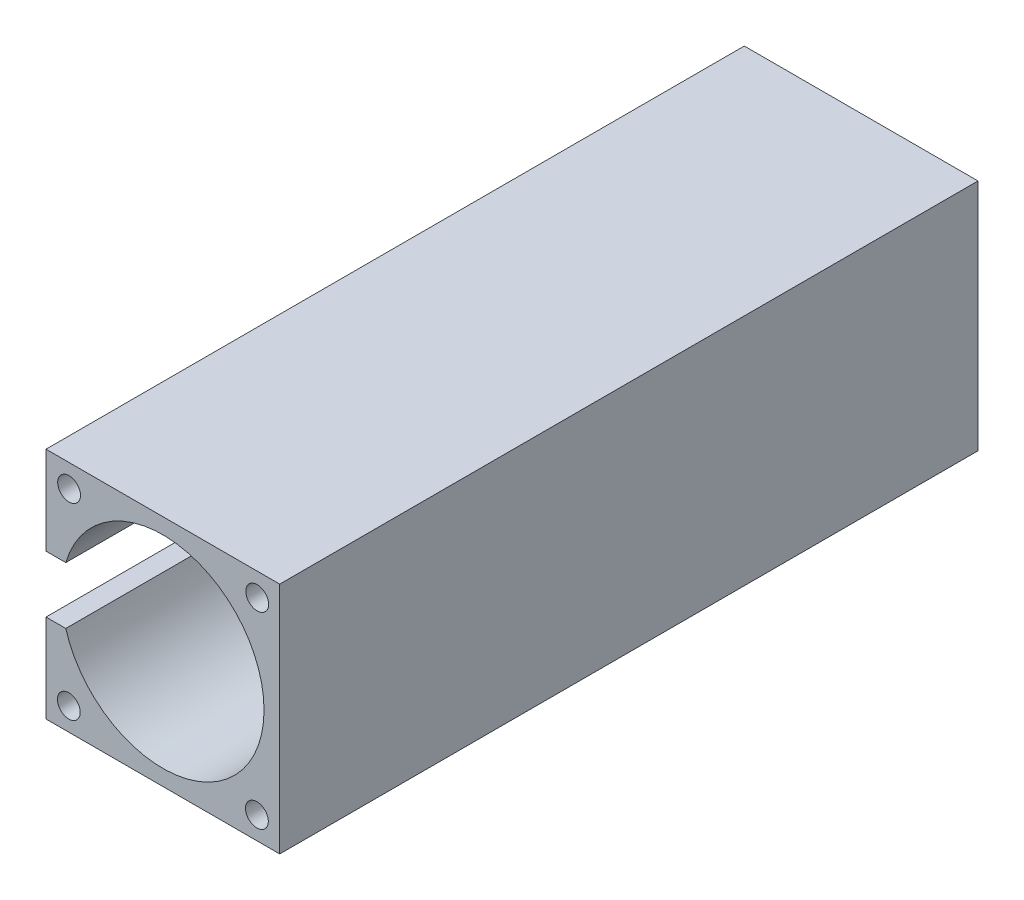
SolidWorks part; units mm, degrees
ref_plane "前基準面" through (0, 0, 0) normal (0, 0, 1) x (1, 0, 0)
ref_plane "上基準面" through (0, 0, 0) normal (0, 1, 0) x (1, 0, 0)
ref_plane "右基準面" through (0, 0, 0) normal (1, 0, 0) x (0, 0, -1)
ref_axis "基準軸1" through (0, -55, 0) along (0, 1, 0)
ref_axis "基準軸2" through (-88.99, 0, 0) along (1, 0, 0)
ref_axis "基準軸3" through (0, 0, 55) along (0, 0, -1)
sketch "草圖1" plane through (0, 0, 0) normal (0, 0, 1) x (1, 0, 0)
  line L0 (0, -55) -> (0, 55) construction
  line L1 (-41, -41) -> (41, -41)
  line L2 (-41, -41) -> (-41, 41)
  line L3 (-41, 41) -> (41, 41)
  line L4 (41, -41) -> (41, 41)
  line L5 (55, 0) -> (-55, 0) construction
  circle A0 centre (0, 0) radius 35.5
  point P7 (0, -41)
  point P10 (41, 0)
  dimension "D1" = 71
  dimension "D2" = 82
  dimension "D3" = 82
extrude "填料-伸長1" add sketch "草圖1" along normal blind 245
sketch "草圖2" plane through (0, 0, 0) normal (0, 0, -1) x (-1, 0, 0)
  line L1 (-41, 41) -> (41, 41)
  line L2 (-41, 41) -> (-41, -41)
  line L3 (-41, -41) -> (41, -41)
  line L4 (41, 41) -> (41, -41)
extrude "填料-伸長2" add sketch "草圖2" along normal blind 27
ref_plane "平面1" through (0, 0, -13.5) normal (0, 0, -1) x (-1, 0, 0)
sketch "草圖3" plane through (0, 0, 245) normal (0, 0, 1) x (1, 0, 0)
  line L0 (-41, 41) -> (-41, -41) construction
  line L1 (-41, 10) -> (-33, 10)
  line L2 (-41, 10) -> (-41, -10)
  line L3 (-41, -10) -> (-33, -10)
  line L4 (-33, 10) -> (-33, -10)
  line L6 (55, 0) -> (-55, 0) construction
  point P6 (-33, 0)
  dimension "D1" = 8
  dimension "D2" = 20
extrude "除料-伸長1" cut sketch "草圖3" against normal up to surface (245 mm away) up to face at (35.5, 0, 0)
sketch "草圖4" plane through (0, 0, 245) normal (0, 0, 1) x (1, 0, 0)
  line L1 (41, 41) -> (-41, 41) construction
  line L2 (-41, 41) -> (-41, 10) construction
  line L3 (-41, -41) -> (41, -41) construction
  line L4 (-41, -10) -> (-41, -41) construction
  circle A0 centre (-32.9, 33) radius 4
  circle A1 centre (33.1, 32.9) radius 4
  circle A2 centre (33, -33.1) radius 4
  circle A3 centre (-33, -33) radius 4
  point P15 (0.05, -0.05)
  dimension "D1" = 8
  dimension "D5" = 8
  dimension "D2" = 8
  dimension "D3" = 8.1
  dimension "D6" = 8
  dimension "D4" = 4
extrude "除料-伸長2" cut sketch "草圖4" against normal blind 20
fillet "圓角2" radius 3 1 edges at (-28.9, 33, 225)
fillet "圓角3" radius 3 1 edges at (37.1, 32.9, 225)
fillet "圓角4" radius 3 1 edges at (-29, -33, 225)
fillet "圓角5" radius 3 1 edges at (37, -33.1, 225)
sketch "草圖5" plane through (0, 41, 0) normal (0, 1, 0) x (1, 0, 0)
  line L0 (-41, -245) -> (-41, 27) construction
  line L4 (-41, 27) -> (41, 27) construction
  circle A2 centre (-36.75, 22.75) radius 1.05
  circle A3 centre (-36.75, 4.75) radius 1.05
  dimension "D1" = 18
  dimension "D2" = 2.1
  dimension "D3" = 2.1
  dimension "D4" = 4.25
  dimension "D5" = 4.25
  dimension "D6" = 4.25
extrude "除料-伸長3" cut sketch "草圖5" against normal blind 10
ref_plane "平面2" through (0, 35, 0) normal (0, 1, 0) x (1, 0, 0)
sketch "草圖6" plane through (0, 35, 0) normal (0, 1, 0) x (1, 0, 0)
  circle A0 centre (-36.75, 22.75) radius 1.05
  circle A1 centre (-36.75, 4.75) radius 1.05
  dimension "D1" = 2.1
  dimension "D2" = 2.1
extrude "填料-伸長3" add sketch "草圖6" along normal blind 0.2
sketch "草圖7" plane through (-41, 0, 0) normal (1, 0, 0) x (0, 0, -1)
  line L1 (27, -41) -> (7, -41)
  line L2 (27, -41) -> (27, 24)
  line L3 (27, 24) -> (7, 24)
  line L4 (7, -41) -> (7, 24)
  dimension "D1" = 20
  dimension "D2" = 65
extrude "除料-伸長5" cut sketch "草圖7" along normal up to next
sketch "草圖8" plane through (0, 41, 0) normal (0, 1, 0) x (1, 0, 0)
  line L0 (0, -45.1) -> (0, 45.1) construction
  line L1 (41, 27) -> (0, 27)
  line L2 (41, 27) -> (41, 7)
  line L3 (41, 7) -> (0, 7)
  line L4 (0, 27) -> (0, 7)
  dimension "D1" = 20
extrude "除料-伸長6" cut sketch "草圖8" against normal up to next
sketch "草圖9" plane through (0, 0, -7) normal (0, 0, -1) x (-1, 0, 0)
  line L0 (-41, -41) -> (-41, 41) construction
  line L1 (-41, -41) -> (41, -41) construction
  line L2 (41, 24) -> (41, -41) construction
  line L3 (0, 41) -> (-41, 41) construction
  line L4 (45.1, 0) -> (-45.1, 0) construction
  circle A0 centre (-33, 33) radius 1.2
  circle A1 centre (-33, -33) radius 1.2
  circle A2 centre (33, -33) radius 1.2
  circle A3 centre (38, 20) radius 1.2
  dimension "D1" = 2.4
  dimension "D2" = 2.4
  dimension "D3" = 2.4
  dimension "D10" = 2.4
  dimension "D4" = 8
  dimension "D5" = 8
  dimension "D6" = 8
  dimension "D7" = 8
  dimension "D8" = 8
  dimension "D9" = 8
  dimension "D11" = 3
  dimension "D12" = 20
extrude "除料-伸長7" cut sketch "草圖9" against normal blind 12
sketch "草圖10" plane through (-41, 0, 0) normal (-1, 0, 0) x (0, 0, 1)
  line L0 (0, -45.1) -> (0, 45.1) construction
  line L1 (0, -41) -> (-27, -41)
  line L2 (0, -41) -> (0, 41)
  line L3 (0, 41) -> (-27, 41)
  line L4 (-27, -41) -> (-27, 41)
  line L5 (0, -55) -> (0, 55) construction
  line L6 (-27, 24) -> (-27, 41) construction
  line L7 (245, 41) -> (-27, 41) construction
  line L8 (245, -41) -> (-7, -41) construction
  point P10 (0, 41)
  point P13 (0, -38.0027)
  dimension "D1" = 0
extrude "除料-伸長8" cut sketch "草圖10" against normal through all both and the other way through all
